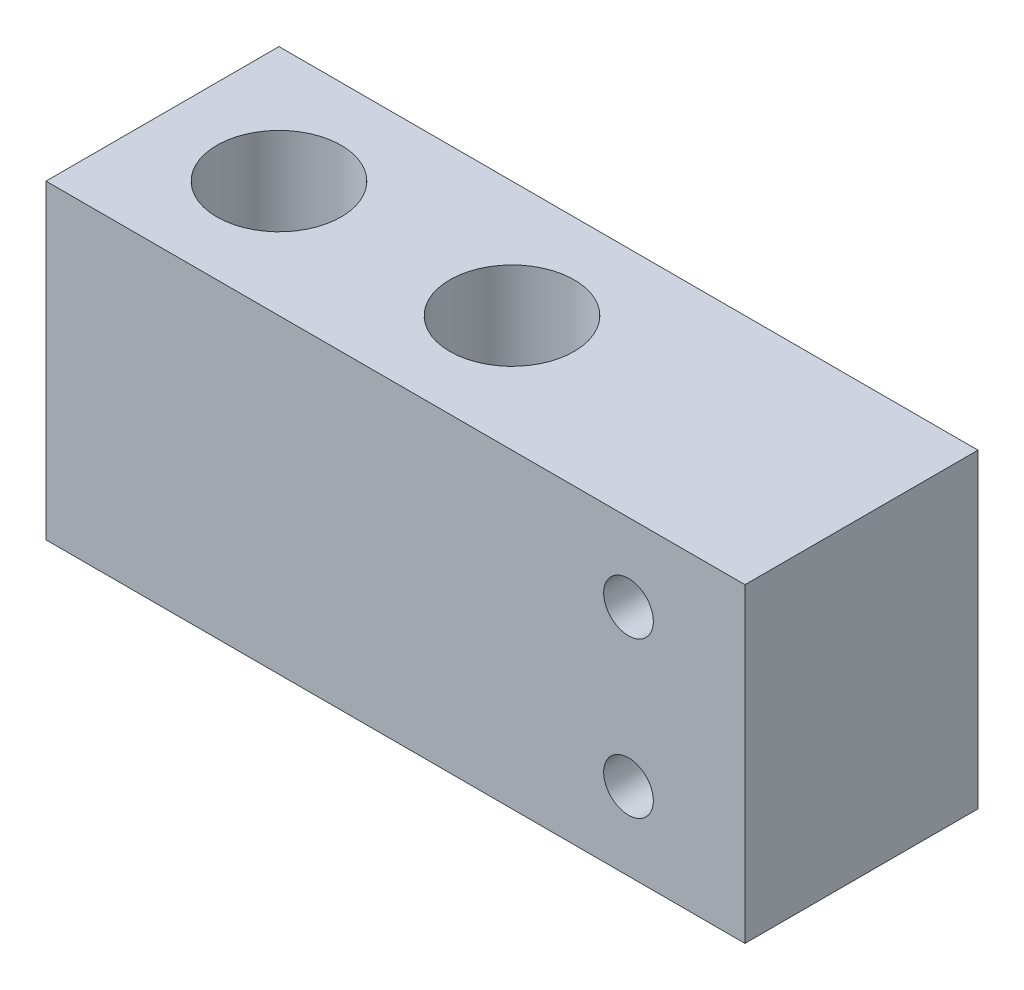
SolidWorks part; units mm, degrees
ref_plane "Front Plane" through (0, 0, 0) normal (0, 0, 1) x (1, 0, 0)
ref_plane "Top Plane" through (0, 0, 0) normal (0, 1, 0) x (1, 0, 0)
ref_plane "Right Plane" through (0, 0, 0) normal (1, 0, 0) x (0, 0, -1)
sketch "Sketch2" plane through (0, 0, 0) normal (0, 1, 0) x (1, 0, 0)
  line L0 (0, 0) -> (-7.5, 0) construction
  line L1 (0, 0) -> (7.5, 0) construction
  line L3 (15, -7.5) -> (-15, -7.5)
  line L4 (15, -7.5) -> (15, 7.5)
  line L5 (15, 7.5) -> (-15, 7.5)
  line L6 (-15, -7.5) -> (-15, 7.5)
  line L7 (15, -7.5) -> (-15, 7.5) construction
  line L8 (15, 7.5) -> (-15, -7.5) construction
  line L9 (-15, 7.5) -> (-30, 7.5)
  line L10 (-15, 7.5) -> (-15, -7.5)
  line L11 (-15, -7.5) -> (-30, -7.5)
  line L12 (-30, 7.5) -> (-30, -7.5)
  line L13 (15, 7.5) -> (30, 7.5)
  line L14 (15, 7.5) -> (15, -7.5)
  line L15 (15, -7.5) -> (30, -7.5)
  line L16 (30, 7.5) -> (30, -7.5)
  circle A0 centre (-7.5, 0) radius 4
  circle A1 centre (7.5, 0) radius 4
  dimension "D3" = 8
  dimension "D4" = 8
  dimension "D1" = 7.5
  dimension "D2" = 7.5
  dimension "D5" = 15
  dimension "D6" = 30
  dimension "D7" = 15
  dimension "D8" = 15
  dimension "D9" = 15
  dimension "D10" = 15
extrude "Boss-Extrude1" add sketch "Sketch2" along normal blind 10 contours L16 L13 L4 L15 | L6 L3 L4 L5 A1 A0 region at (0, 0, 0) region at (22.5, 0, 0)
extrude "Boss-Extrude2" add sketch "Sketch2<3>" against normal blind 10 contours L16 L13 L4 L15 | L6 L3 L4 L5 A1 A0 region at (0, 0, 0) region at (22.5, 0, 0)
sketch "Sketch2<3>" plane through (0, 0, 0) normal (0, 1, 0) x (1, 0, 0) same geometry as "Sketch2"
sketch "Sketch4" plane through (0, 0, 7.5) normal (0, 0, 1) x (1, 0, 0)
  line L0 (-30, 0) -> (-22.5, 0) construction
  line L1 (-30, 10) -> (-30, -10) construction
  line L2 (30, 0) -> (22.5, 0) construction
  line L3 (30, 10) -> (30, -10) construction
  line L4 (-22.5, -5) -> (-22.5, 5) construction
  line L5 (22.5, -5) -> (22.5, 5) construction
  line L7 (-22.5, 8.4352) -> (-25.475, 6.7176)
  line L8 (-25.475, 6.7176) -> (-25.475, 3.2824)
  line L9 (-25.475, 3.2824) -> (-22.5, 1.5648)
  line L10 (-22.5, 1.5648) -> (-19.525, 3.2824)
  line L11 (-19.525, 3.2824) -> (-19.525, 6.7176)
  line L12 (-19.525, 6.7176) -> (-22.5, 8.4352)
  line L13 (22.5, 8.4352) -> (19.525, 6.7176)
  line L14 (19.525, 6.7176) -> (19.525, 3.2824)
  line L15 (19.525, 3.2824) -> (22.5, 1.5648)
  line L16 (22.5, 1.5648) -> (25.475, 3.2824)
  line L17 (25.475, 3.2824) -> (25.475, 6.7176)
  line L18 (25.475, 6.7176) -> (22.5, 8.4352)
  line L19 (-22.5, -8.4352) -> (-19.525, -6.7176)
  line L20 (22.5, -8.4352) -> (25.475, -6.7176)
  line L21 (25.475, -6.7176) -> (25.475, -3.2824)
  line L22 (25.475, -3.2824) -> (22.5, -1.5648)
  line L23 (22.5, -1.5648) -> (19.525, -3.2824)
  line L24 (19.525, -3.2824) -> (19.525, -6.7176)
  line L25 (19.525, -6.7176) -> (22.5, -8.4352)
  line L26 (-19.525, -6.7176) -> (-19.525, -3.2824)
  line L27 (-19.525, -3.2824) -> (-22.5, -1.5648)
  line L28 (-22.5, -1.5648) -> (-25.475, -3.2824)
  line L29 (-25.475, -3.2824) -> (-25.475, -6.7176)
  line L30 (-25.475, -6.7176) -> (-22.5, -8.4352)
  circle A0 centre (22.5, 5) radius 1.6
  circle A1 centre (22.5, -5) radius 1.6
  circle A2 centre (-22.5, -5) radius 1.6
  circle A3 centre (-22.5, 5) radius 1.6
  circle A4 centre (-22.5, 5) radius 2.975 construction
  circle A5 centre (22.5, 5) radius 2.975 construction
  circle A6 centre (22.5, -5) radius 2.975 construction
  circle A7 centre (-22.5, -5) radius 2.975 construction
  point P12 (-22.5, 0)
  point P15 (22.5, 0)
  dimension "D5" = 3.2
  dimension "D6" = 3.2
  dimension "D7" = 3.2
  dimension "D8" = 3.2
  dimension "D9" = 5.95
  dimension "D10" = 5.95
  dimension "D11" = 5.95
  dimension "D12" = 5.95
  dimension "D1" = 7.5
  dimension "D2" = 7.5
  dimension "D3" = 10
  dimension "D4" = 10
extrude "Cut-Extrude1" cut sketch "Sketch4" against normal through all contours A2 | A3 | A0 | A1 region at (22.5, 5, 7.5) region at (22.5, -5, 7.5) region at (-22.5, -5, 7.5) region at (-22.5, 5, 7.5)
extrude "Cut-Extrude2" cut sketch "Sketch4<3>" against normal blind 2.5 from offset 6.25 offset against normal yes
sketch "Sketch4<3>" plane through (0, 0, 7.5) normal (0, 0, 1) x (1, 0, 0) same geometry as "Sketch4"
